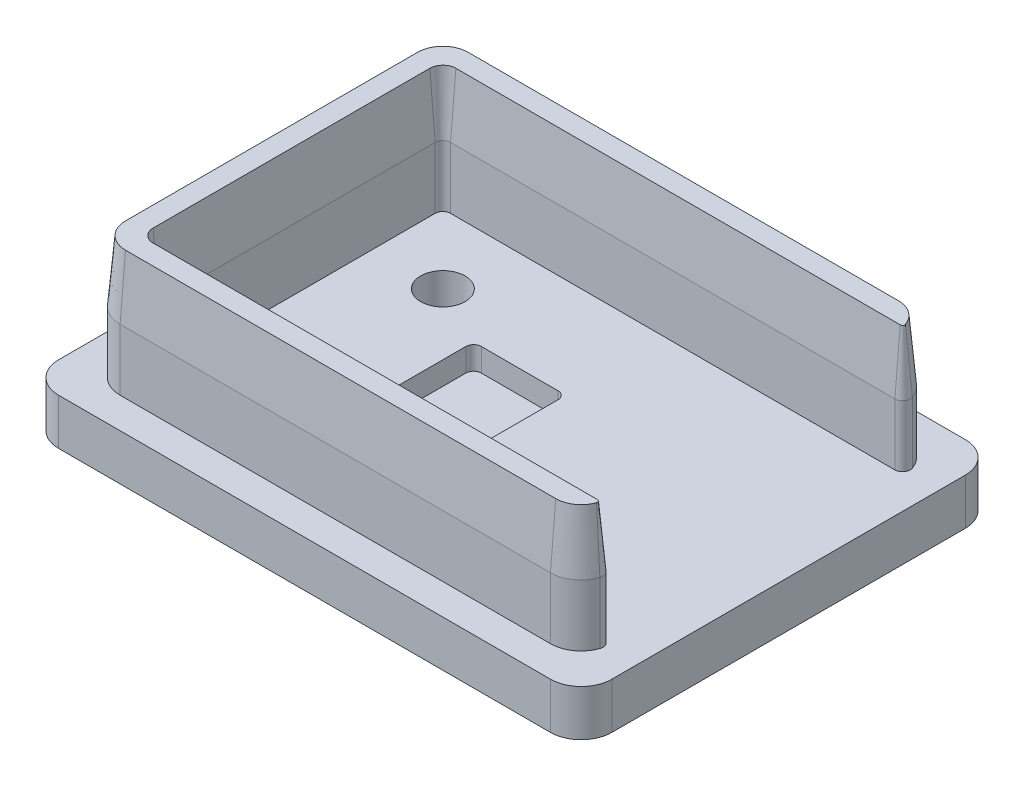
SolidWorks part; units mm, degrees
ref_plane "Front Plane" through (0, 0, 0) normal (0, 0, 1) x (1, 0, 0)
ref_plane "Top Plane" through (0, 0, 0) normal (0, 1, 0) x (1, 0, 0)
ref_plane "Right Plane" through (0, 0, 0) normal (1, 0, 0) x (0, 0, -1)
sketch "Sketch1" plane through (0, 0, 0) normal (0, 1, 0) x (1, 0, 0)
  line L1 (-18, -13.5) -> (18, -13.5)
  line L2 (-18, -13.5) -> (-18, 13.5)
  line L3 (-18, 13.5) -> (18, 13.5)
  line L4 (18, -13.5) -> (18, 13.5)
  line L5 (-18, -13.5) -> (18, 13.5) construction
  line L6 (-18, 13.5) -> (18, -13.5) construction
  point P0 (0, 0)
  dimension "D1" = 36
  dimension "D2" = 27
extrude "Boss-Extrude1" add sketch "Sketch1" along normal blind 3
sketch "Sketch2" plane through (0, 3, 0) normal (0, 1, 0) x (1, 0, 0)
  line L0 (-2.5, 13.5) -> (-2.5, -13.5) construction
  line L1 (18, 13.5) -> (-18, 13.5) construction
  line L2 (-18, -13.5) -> (18, -13.5) construction
  line L3 (-18, 0) -> (18, 0) construction
  line L4 (-18, 13.5) -> (-18, -13.5) construction
  line L5 (18, -13.5) -> (18, 13.5) construction
  line L7 (-5.5, -3) -> (0.5, -3)
  line L8 (-5.5, -3) -> (-5.5, 3)
  line L9 (-5.5, 3) -> (0.5, 3)
  line L10 (0.5, -3) -> (0.5, 3)
  line L11 (-5.5, -3) -> (0.5, 3) construction
  line L12 (-5.5, 3) -> (0.5, -3) construction
  point P12 (-2.5, 0)
  dimension "D1" = 20.5
  dimension "D2" = 6
  dimension "D3" = 6
extrude "Cut-Extrude1" cut sketch "Sketch2" against normal blind 1.5
sketch "Sketch3" plane through (0, 3, 0) normal (0, 1, 0) x (1, 0, 0)
  line L0 (-9.5, 13.5) -> (-9.5, -13.5) construction
  line L1 (18, 13.5) -> (-18, 13.5) construction
  line L2 (-18, -13.5) -> (18, -13.5) construction
  line L3 (-18, 13.5) -> (-18, -13.5) construction
  line L4 (18, 0) -> (-18, 0) construction
  line L5 (18, -13.5) -> (18, 13.5) construction
  line L6 (-2.5, 3) -> (-2.5, -3) construction
  line L7 (0.5, 3) -> (-5.5, 3) construction
  line L8 (-5.5, -3) -> (0.5, -3) construction
  circle A0 centre (-9.5, 5) radius 1.45
  circle A1 centre (-9.5, -5) radius 1.45
  dimension "D2" = 2.9
  dimension "D1" = 7
  dimension "D3" = 5
extrude "Cut-Extrude2" cut sketch "Sketch3" against normal blind 2.3
sketch "Sketch4" plane through (0, 3, 0) normal (0, 1, 0) x (1, 0, 0)
  line L10 (-16, 11.5) -> (-16, -11.5)
  line L11 (-16, -11.5) -> (16, -11.5)
  line L13 (16, 11.5) -> (-16, 11.5)
  line L15 (18, 13.5) -> (-18, 13.5) construction
  line L16 (-18, 13.5) -> (-18, -13.5) construction
  line L17 (-18, -13.5) -> (18, -13.5) construction
  line L18 (16, 11.5) -> (16, -11.5) construction
  line L19 (16, 11.5) -> (16, 9.5)
  line L20 (16, 9.5) -> (-14, 9.5)
  line L21 (-14, 9.5) -> (-14, -9.5)
  line L22 (-14, -9.5) -> (16, -9.5)
  line L23 (16, -9.5) -> (16, -11.5)
  line L24 (18, -13.5) -> (18, 13.5) construction
  dimension "D1" = 2
  dimension "D2" = 2
  dimension "D3" = 2
  dimension "D4" = 2
  dimension "D5" = 2
  dimension "D6" = 2
  dimension "D7" = 2
extrude "Boss-Extrude3" add sketch "Sketch4" along normal blind 8
fillet "Fillet1" radius 2 8 edges at (-16, 7, -11.5) (16, 7, -11.5) (16, 7, 11.5) (-16, 7, 11.5) (-18, 1.5, 13.5) (18, 1.5, 13.5) (-18, 1.5, -13.5) (18, 1.5, -13.5)
fillet "Fillet2" radius 0.5 2 edges at (-14, 7, -9.5) (-14, 7, 9.5)
fillet "Fillet3" radius 0.5 6 edges at (16, 7, -9.5) (16, 7, 9.5) (0.5, 2.25, 3) (0.5, 2.25, -3) (-5.5, 2.25, -3) (-5.5, 2.25, 3)
chamfer "Chamfer2" distance 4 angle 5 14 edges at (15.1547, 11, 11.133) (0, 11, 11.5) (-15.4142, 11, 10.9142) (-16, 11, 0) (15.1547, 11, -11.133) (-15.4142, 11, -10.9142) (0, 11, -11.5) (0.9571, 11, 9.5) (-13.8536, 11, 9.3536) (15.8225, 11, 9.7113) (-14, 11, 0) (-13.8536, 11, -9.3536) (0.9571, 11, -9.5) (15.8225, 11, -9.7113) first distance on face at (15.0488, 7, 10.9832) first distance on face at (0, 7, 11.5) first distance on face at (-15.2071, 7, 10.7071) first distance on face at (-16, 7, 0) first distance on face at (15.0488, 7, -10.9832) first distance on face at (-15.2071, 7, -10.7071) first distance on face at (0, 7, -11.5) first distance on face at (0.9571, 7, 9.5) first distance on face at (-13.8018, 7, 9.3018) first distance on face at (15.7362, 7, 9.7723) first distance on face at (-14, 7, 0) first distance on face at (-13.8018, 7, -9.3018) first distance on face at (0.9571, 7, -9.5) first distance on face at (15.7362, 7, -9.7723)
